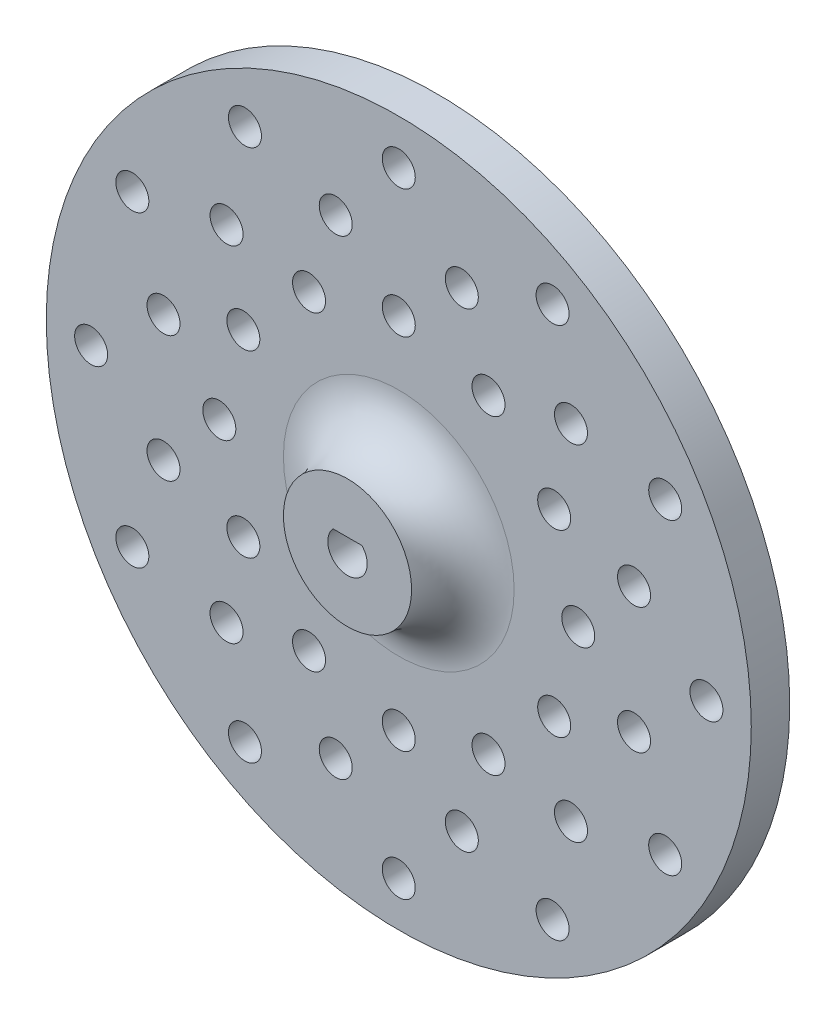
SolidWorks part; units mm, degrees
ref_plane "Plano frontal" through (0, 0, 0) normal (0, 0, 1) x (1, 0, 0)
ref_plane "Plano superior" through (0, 0, 0) normal (0, 1, 0) x (1, 0, 0)
ref_plane "Plano direito" through (0, 0, 0) normal (1, 0, 0) x (0, 0, -1)
sketch "Esboço1" plane through (0, 0, 0) normal (0, 0, 1) x (1, 0, 0)
  circle A0 centre (0, 0) radius 55
  dimension "D1" = 110
extrude "Ressalto-extrusão1" add sketch "Esboço1" along normal blind 6
sketch "Esboço2" plane through (0, 0, 6) normal (0, 0, 1) x (1, 0, 0)
  line L0 (-2.2462, 2.1) -> (2.2462, 2.1)
  line L1 (0, 0) -> (0, 2.1) construction
  arc A0 (-2.2462, 2.1) -> (2.2462, 2.1) centre (0, 0) ccw
  circle A1 centre (0, 0) radius 10
  dimension "D2" = 6.15
  dimension "D3" = 20
  dimension "D1" = 2.1
extrude "Ressalto-extrusão2" add sketch "Esboço2" along normal blind 8
fillet "Filete3" radius 8 1 edges at (10, 0, 6)
sketch "Esboço3" plane through (0, 0, 6) normal (0, 0, 1) x (1, 0, 0)
  line L0 (0, 0) -> (0, 48)
  circle A0 centre (0, 48) radius 2.575
  dimension "D1" = 5.15
  dimension "D2" = 48
extrude "Corte-extrusão1" cut sketch "Esboço3" against normal through all contours A0 region at (1.7693, 46.2307, 6)
pattern_circular "PadrãoCircular1" count 12 over 360 about axis through (0, 0, 6) along (0, 0, -1) of "Corte-extrusão1"
sketch "Esboço4" plane through (0, 0, 6) normal (0, 0, 1) x (1, 0, 0)
  line L1 (2.2462, 2.1) -> (-2.2462, 2.1)
  line L2 (2.2462, 2.1) -> (-2.2462, 2.1)
  arc A1 (-2.2462, 2.1) -> (2.2462, 2.1) centre (0, 0) ccw
  arc A2 (-2.2462, 2.1) -> (2.2462, 2.1) centre (0, 0) ccw
  dimension "D1" = 0
extrude "Corte-extrusão2" cut sketch "Esboço4" against normal through all
sketch "Esboço5" plane through (0, 0, 6) normal (0, 0, 1) x (1, 0, 0)
  line L0 (0, 0) -> (0, 48) construction
  line L1 (0, 48) -> (24, 41.5692) construction
  line L2 (24, 41.5692) -> (0, 0) construction
  line L3 (12, 44.7846) -> (0, 0) construction
  line L4 (0, 0) -> (9.8351, 36.7052)
  circle A0 centre (9.8351, 36.7052) radius 2.575
  circle A1 centre (24, 41.5692) radius 2.575 construction
  dimension "D1" = 38
extrude "Corte-extrusão3" cut sketch "Esboço5" against normal through all contours A0 region at (11.3583, 34.7201, 6)
pattern_circular "PadrãoCircular2" count 12 over 360 about axis through (0, 0, 14) along (0, 0, 1) of "Corte-extrusão3"
sketch "Esboço6" plane through (0, 0, 6) normal (0, 0, 1) x (1, 0, 0)
  line L0 (0, 0) -> (0, 28)
  circle A0 centre (0, 28) radius 2.575
  circle A1 centre (9.8351, 36.7052) radius 2.575 construction
  dimension "D1" = 28
extrude "Corte-extrusão4" cut sketch "Esboço6" against normal through all contours A0 region at (1.7693, 26.2307, 6)
pattern_circular "PadrãoCircular3" count 12 over 360 about axis through (0, 0, 14) along (0, 0, 1) of "Corte-extrusão4"
equation "\"n\"= 12"
equation "\"D1@PadrãoCircular1\"=\"n\""
equation "\"D1@PadrãoCircular2\"=\"n\""
equation "\"D1@PadrãoCircular3\"=\"n\""
equation "\"d1\"= 48mm"
equation "\"d2\"= 38mm"
equation "\"d3\"= 28mm"
equation "\"D2@Esboço3\"=\"d1\""
equation "\"D1@Esboço6\"=\"d3\""
equation "\"D1@Esboço5\"=\"d2\""
